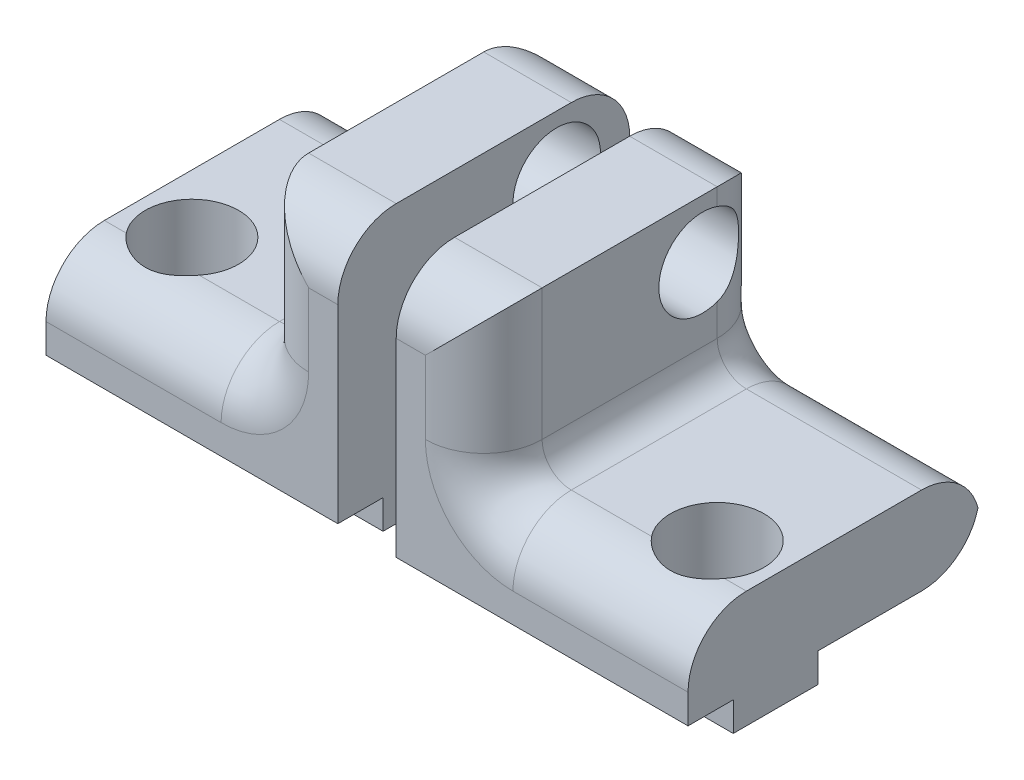
SolidWorks part; units mm, degrees
ref_plane "Front Plane" through (0, 0, 0) normal (0, 0, 1) x (1, 0, 0)
ref_plane "Top Plane" through (0, 0, 0) normal (0, 1, 0) x (1, 0, 0)
ref_plane "Right Plane" through (0, 0, 0) normal (1, 0, 0) x (0, 0, -1)
sketch "Esquisse1" plane through (0, 0, 0) normal (0, 0, 1) x (1, 0, 0)
  line L0 (0, 0) -> (10, 0)
  line L1 (10, 0) -> (10, 3)
  line L2 (10, 3) -> (4, 3)
  line L4 (3, 4) -> (3, 8.5)
  line L5 (3, 8.5) -> (0, 8.5)
  line L6 (0, 8.5) -> (0, 0)
  arc A0 (4, 3) -> (3, 4) centre (4, 4) cw
  dimension "D1" = 1
  dimension "D2" = 8.5
  dimension "D3" = 3
  dimension "D4" = 10
extrude "Main" add sketch "Esquisse1" along normal mid plane 10
sketch "Esquisse2" plane through (0, 0, 0) normal (-1, 0, 0) x (0, 0, 1)
  line L1 (5, 8.5) -> (-5, 8.5) construction
  line L2 (-5, 4) -> (-5, 8.5) construction
  line L3 (5, 3) -> (-5, 3) construction
  circle A0 centre (-2.5, 6.5) radius 1.5
  point P2 (-0.2121, 10)
  point P9 (0, 8.5)
  dimension "D1" = 3
  dimension "D2" = 3.5
  dimension "D3" = 2.5
extrude "VerticalHole" cut sketch "Esquisse2" against normal through all both and the other way through all
sketch "Esquisse5" plane through (0, 0, 0) normal (0, -1, 0) x (-1, 0, 0)
  line L0 (-10, -5) -> (-10, 5) construction
  line L1 (0, -0.55) -> (-10, -0.55)
  line L2 (0, -0.55) -> (0, -3.45)
  line L3 (0, -3.45) -> (-10, -3.45)
  line L4 (-10, -0.55) -> (-10, -3.45)
  line L6 (0, -5) -> (-10, -5) construction
  line L7 (0, -5) -> (0, 5) construction
  point P9 (0, -0.45)
  dimension "D1" = 2.9
  dimension "D2" = 1.55
extrude "MakerBeamSupport" add sketch "Esquisse5" along normal blind 1
sketch "Esquisse3" plane through (0, 0, 0) normal (0, -1, 0) x (1, 0, 0)
  line L0 (10, 5) -> (10, 3.45) construction
  line L4 (10, 0.55) -> (10, 3.45) construction
  circle A0 centre (8, 2) radius 1.6
  point P2 (10, 2)
  point P3 (0, 0)
  point P8 (0, 0)
  dimension "D1" = 3.2
  dimension "D2" = 2
extrude "MakerBeamHole" cut sketch "Esquisse3" against normal through all both and the other way through all
fillet "Fillet1" radius 2 9 edges at (3, 6.25, -5) (3.2929, 3.2929, -5) (3, 6.25, 5) (3.2929, 3.2929, 5) (7, 3, -5) (7, 3, 5) (1.5, 8.5, -5) (1.5, 8.5, 5) (5, 0, -5)
ref_plane "Plane1" through (-1, 0, 0) normal (-1, 0, 0) x (0, 0, 1)
mirror "Mirror2" about plane through (-1, 0, 0) normal (-1, 0, 0) of bodies 110
